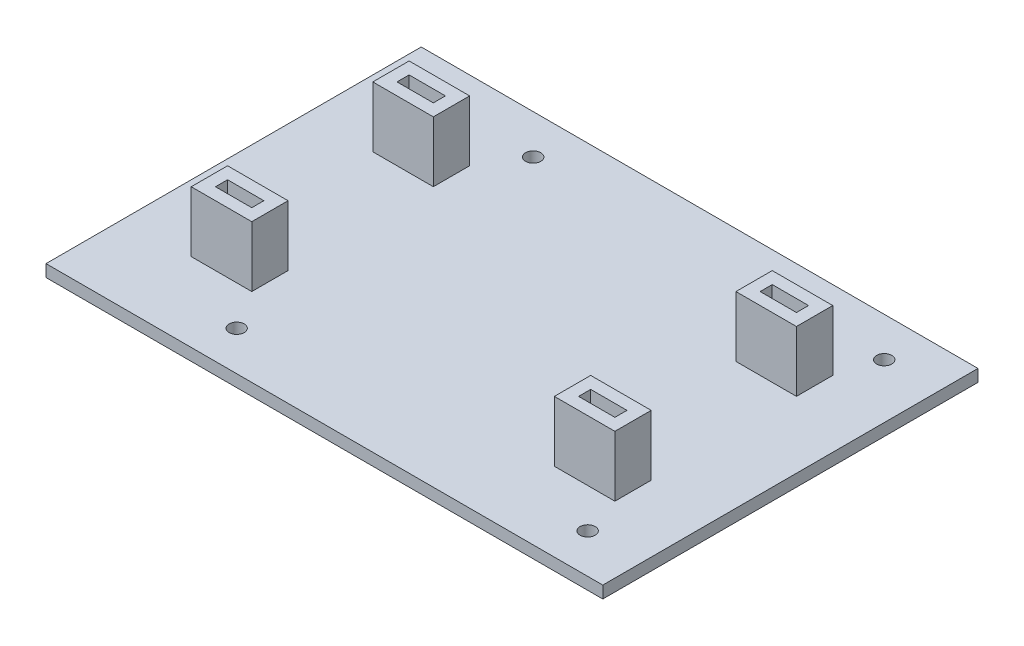
SolidWorks part; units mm, degrees
ref_plane "前视基准面" through (0, 0, 0) normal (0, 0, 1) x (1, 0, 0)
ref_plane "上视基准面" through (0, 0, 0) normal (0, 1, 0) x (1, 0, 0)
ref_plane "右视基准面" through (0, 0, 0) normal (1, 0, 0) x (0, 0, -1)
sketch "草图1" plane through (0, 0, 0) normal (0, 1, 0) x (1, 0, 0)
  line L1 (-46, 31) -> (46, 31)
  line L2 (-46, 31) -> (-46, -31)
  line L3 (-46, -31) -> (46, -31)
  line L4 (46, 31) -> (46, -31)
  line L5 (-46, 31) -> (46, -31) construction
  line L6 (-46, -31) -> (46, 31) construction
  point P0 (0, 0)
  dimension "D1" = 62
  dimension "D2" = 92
extrude "底板" add sketch "草图1" along normal blind 2
sketch "草图2" plane through (0, 2, 0) normal (0, 1, 0) x (1, 0, 0)
  line L0 (46, -31) -> (46, 31) construction
  line L1 (-21, 24.5) -> (37, 24.5)
  line L2 (-21, 24.5) -> (-21, -24.5)
  line L3 (-21, -24.5) -> (37, -24.5)
  line L4 (37, 24.5) -> (37, -24.5)
  circle A0 centre (-21, 24.5) radius 1.25
  circle A1 centre (37, 24.5) radius 1.25
  circle A2 centre (-21, -24.5) radius 1.25
  circle A3 centre (37, -24.5) radius 1.25
  point P0 (0, 0)
  dimension "D3" = 2.5
  dimension "D4" = 2.5
  dimension "D5" = 2.5
  dimension "D6" = 2.5
  dimension "D1" = 49
  dimension "D2" = 58
  dimension "D7" = 9
extrude "螺丝孔" cut sketch "草图2" against normal blind 2 contours A0 | A2 | A3 | A1
sketch "草图3" plane through (0, 2, 0) normal (0, 1, 0) x (1, 0, 0)
  line L1 (30, 15) -> (-30, 15)
  line L2 (30, 15) -> (30, -15)
  line L3 (30, -15) -> (-30, -15)
  line L4 (-30, 15) -> (-30, -15)
  line L5 (30, 15) -> (-30, -15) construction
  line L6 (30, -15) -> (-30, 15) construction
  line L7 (-27, 16) -> (-33, 16)
  line L8 (-27, 16) -> (-27, 14)
  line L9 (-27, 14) -> (-33, 14)
  line L10 (-33, 16) -> (-33, 14)
  line L11 (-27, 16) -> (-33, 14) construction
  line L12 (-27, 14) -> (-33, 16) construction
  line L13 (-25, 18) -> (-35, 18)
  line L14 (-25, 18) -> (-25, 12)
  line L15 (-25, 12) -> (-35, 12)
  line L16 (-35, 18) -> (-35, 12)
  line L17 (-25, 18) -> (-35, 12) construction
  line L18 (-25, 12) -> (-35, 18) construction
  line L19 (-25, -18) -> (-35, -18)
  line L20 (-25, -18) -> (-25, -12)
  line L21 (-25, -12) -> (-35, -12)
  line L22 (-35, -18) -> (-35, -12)
  line L23 (-25, -18) -> (-35, -12) construction
  line L24 (-25, -12) -> (-35, -18) construction
  line L25 (-27, -16) -> (-33, -16)
  line L26 (-27, -16) -> (-27, -14)
  line L27 (-27, -14) -> (-33, -14)
  line L28 (-33, -16) -> (-33, -14)
  line L29 (-27, -16) -> (-33, -14) construction
  line L30 (-27, -14) -> (-33, -16) construction
  line L31 (25, -12) -> (35, -12)
  line L32 (25, -12) -> (25, -18)
  line L33 (25, -18) -> (35, -18)
  line L34 (35, -12) -> (35, -18)
  line L35 (25, -12) -> (35, -18) construction
  line L36 (25, -18) -> (35, -12) construction
  line L37 (27, -16) -> (33, -16)
  line L38 (27, -16) -> (27, -14)
  line L39 (27, -14) -> (33, -14)
  line L40 (33, -16) -> (33, -14)
  line L41 (27, -16) -> (33, -14) construction
  line L42 (27, -14) -> (33, -16) construction
  line L43 (25, 18) -> (35, 18)
  line L44 (25, 18) -> (25, 12)
  line L45 (25, 12) -> (35, 12)
  line L46 (35, 18) -> (35, 12)
  line L47 (25, 18) -> (35, 12) construction
  line L48 (25, 12) -> (35, 18) construction
  line L49 (27, 14) -> (33, 14)
  line L50 (27, 14) -> (27, 16)
  line L51 (27, 16) -> (33, 16)
  line L52 (33, 14) -> (33, 16)
  line L53 (27, 14) -> (33, 16) construction
  line L54 (27, 16) -> (33, 14) construction
  point P0 (0, 0)
  dimension "D1" = 60
  dimension "D2" = 30
  dimension "D3" = 2
  dimension "D4" = 6
  dimension "D5" = 10
  dimension "D6" = 6
  dimension "D7" = 10
  dimension "D8" = 6
  dimension "D9" = 2
  dimension "D10" = 6
  dimension "D11" = 2
  dimension "D12" = 6
  dimension "D13" = 10
  dimension "D14" = 6
  dimension "D15" = 2
  dimension "D16" = 6
  dimension "D17" = 10
  dimension "D18" = 6
extrude "连接口" add sketch "草图3" along normal blind 10 contours L13 L16 L15 L4 L9 L10 L7 L8 L1 L14 | L15 L14 L1 L8 L9 L4 | L25 L28 L27 L4 L21 L22 L19 L20 L3 L26 | L27 L26 L3 L20 L21 L4 | L40 L37 L38 L3 L32 L33 L34 L31 L2 L39 | L38 L39 L2 L31 L32 L3 | L52 L49 L2 L45 L46 L43 L44 L1 L50 L51 | L49 L50 L1 L44 L45 L2 region at (27.25, 2, -13.25) region at (26, 2, -15.1166) region at (-27.25, 2, -13.25) region at (-26, 2, -15.1166) region at (32.5, 2, 12.1166) region at (27.25, 2, 13.25) region at (-27.25, 2, 13.25) region at (-30.1166, 2, 13)
